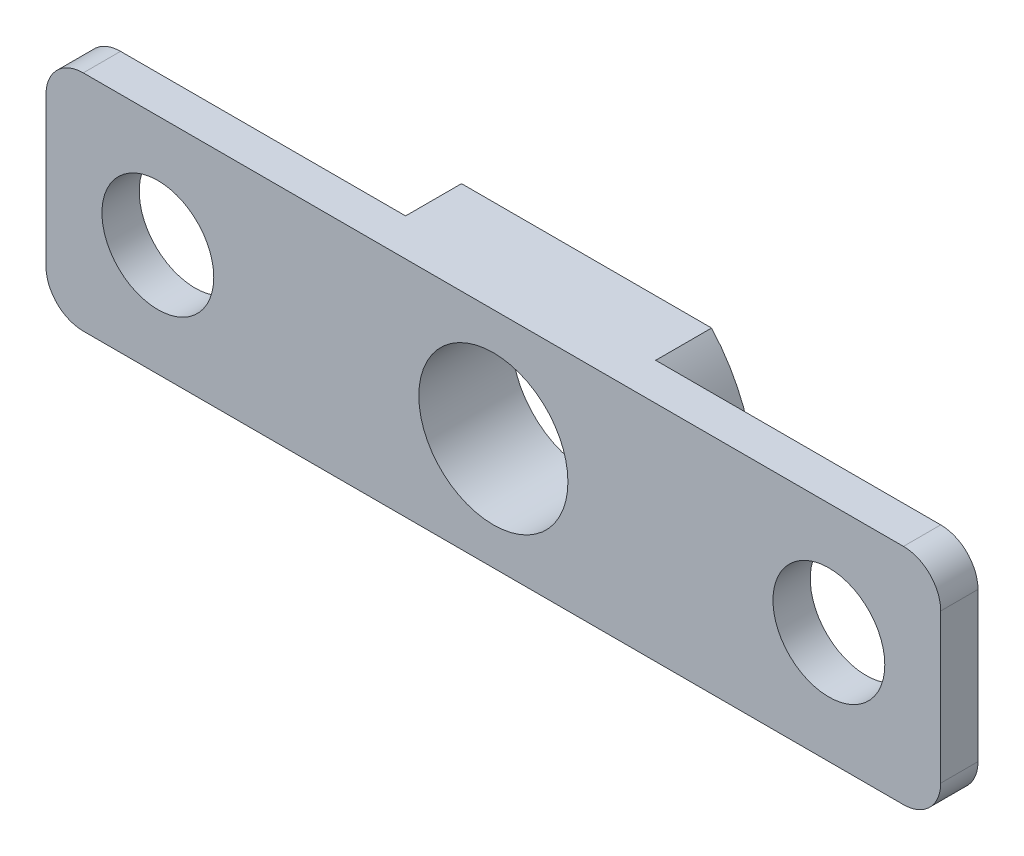
SolidWorks part; units mm, degrees
ref_plane "Front Plane" through (0, 0, 0) normal (0, 0, 1) x (1, 0, 0)
ref_plane "Top Plane" through (0, 0, 0) normal (0, 1, 0) x (1, 0, 0)
ref_plane "Right Plane" through (0, 0, 0) normal (1, 0, 0) x (0, 0, -1)
sketch "Sketch1" plane through (0, 0, 0) normal (0, 0, 1) x (1, 0, 0)
  line L1 (-3, 3) -> (21, 3)
  line L2 (-3, 3) -> (-3, -3)
  line L3 (-3, -3) -> (21, -3)
  line L4 (21, 3) -> (21, -3)
  circle A0 centre (0, 0) radius 1.5
  circle A2 centre (18, 0) radius 1.5
  circle A3 centre (9, 0) radius 2
  circle A4 centre (9, 0) radius 1.5 [skipped]
  dimension "D1" = 3
  dimension "D7" = 4
  dimension "D3" = 12
  dimension "D4" = 12
  dimension "D5" = 3
  dimension "D6" = 3
  dimension "D2" = 3
extrude "Boss-Extrude2" add sketch "Sketch1" along normal blind 1
fillet "Fillet1" radius 1 1 edges at (-3, 3, 0.5)
fillet "Fillet2" radius 1 3 edges at (21, 3, 0.5) (21, -3, 0.5) (-3, -3, 0.5)
ref_plane "Plane1" through (0, 0, 0) normal (0, 0, -1) x (-1, 0, 0)
sketch "Sketch2" plane through (0, 0, 0) normal (0, 0, -1) x (-1, 0, 0)
  line L0 (2, -3) -> (-20, -3) construction
  line L1 (-20, 3) -> (2, 3) construction
  line L2 (-5.6459, -3) -> (-12.3541, -3)
  line L3 (-12.3541, 3) -> (-5.6459, 3)
  circle A1 centre (-9, 0) radius 1.5
  arc A2 (-12.3541, 3) -> (-12.3541, -3) centre (-9, 0) ccw
  circle A3 centre (-9, 0) radius 4.5 construction
  arc A4 (-5.6459, -3) -> (-5.6459, 3) centre (-9, 0) ccw
  circle A5 centre (-9, 0) radius 2
  dimension "D1" = 3
  dimension "D2" = 4
  dimension "D3" = 3
extrude "Boss-Extrude3" add sketch "Sketch2" along normal blind 1.5 contours L2 A4 L3 A2 A5 region at (9, -2.8918, 0)
